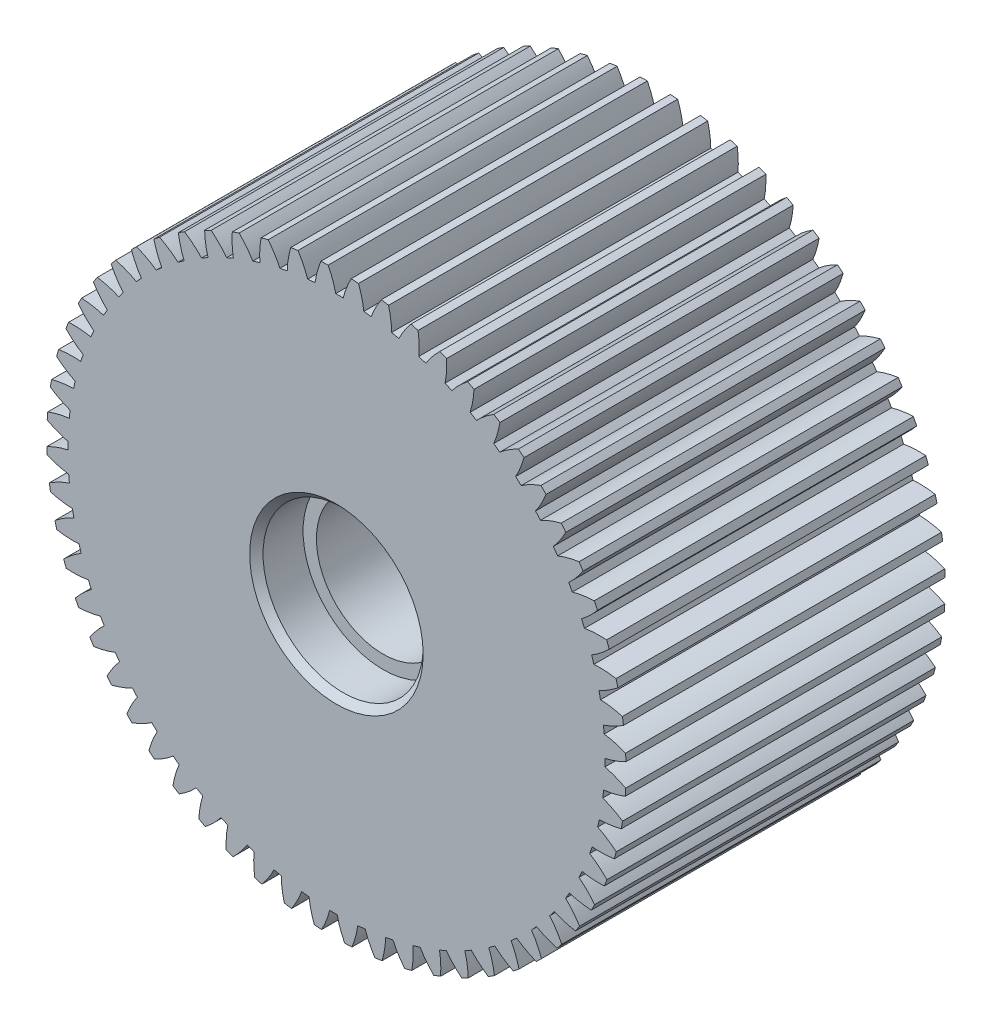
SolidWorks part; units mm, degrees
material "PLA"
ref_plane "Front Plane" through (0, 0, 0) normal (0, 0, 1) x (1, 0, 0)
ref_plane "Top Plane" through (0, 0, 0) normal (0, 1, 0) x (1, 0, 0)
ref_plane "Right Plane" through (0, 0, 0) normal (1, 0, 0) x (0, 0, -1)
sketch "Sketch1" plane through (0, 0, 0) normal (0, 0, 1) x (1, 0, 0)
  circle A0 centre (0, 0) radius 21.7
  dimension "D1" = 43.4
extrude "Boss-Extrude1" add sketch "Sketch1" along normal mid plane 23.9129
sketch "Sketch2" plane through (0, 0, 0) normal (0, 0, 1) x (1, 0, 0)
  line L0 (0, 0) -> (19.7335, 0) construction
  line L1 (0, 0) -> (20.9987, -0.2368) construction
  line L2 (0, 0) -> (19.7285, -0.445) construction
  line L3 (19.7335, 0) -> (20.125, 0)
  line L4 (19.7285, -0.445) -> (20.1199, -0.4538)
  circle A0 centre (0, 0) radius 21 construction
  circle A1 centre (0, 0) radius 19.7335 construction
  circle A2 centre (0, 0) radius 20.125
  circle A3 centre (0, 0) radius 21.7 construction
  circle A4 centre (0, 0) radius 21.7
  spline S0 degree 4 poles (19.7335, 0) (19.7403, 0.0001) (19.7592, 0.0007) (19.7949, 0.0029) (19.8532, 0.0083) (19.9272, 0.0177) (20.0227, 0.0326) (20.1349, 0.0538) (20.2577, 0.0809) (20.3908, 0.1144) (20.523, 0.1515) (20.6543, 0.1919) (20.7846, 0.2351) (20.9418, 0.291) (21.1292, 0.3629) (21.3467, 0.4541) (21.5913, 0.5659) (21.8383, 0.6888) (22.0793, 0.8169) (22.3203, 0.9546) (22.5517, 1.0937) (22.7893, 1.2466) (23.0071, 1.3919) (23.2479, 1.5639) (23.4412, 1.7054) (23.6925, 1.9016) (23.8398, 2.0204) (24.0108, 2.1626) (24.086, 2.2275) (24.1324, 2.2674) knots 0 0 0 0 0 0.005377 0.015084 0.028532 0.04661 0.064855 0.092111 0.119476 0.146842 0.174209 0.201575 0.228941 0.256307 0.307035 0.361767 0.4165 0.471232 0.525964 0.580697 0.635429 0.690161 0.744894 0.799626 0.854358 0.909091 0.954545 1 1 1 1 1 construction
  spline S1 degree 4 poles (19.7335, 0) (19.7403, 0.0001) (19.7592, 0.0007) (19.7949, 0.0029) (19.8532, 0.0083) (19.9272, 0.0177) (20.0227, 0.0326) (20.1349, 0.0538) (20.2577, 0.0809) (20.3908, 0.1144) (20.523, 0.1515) (20.6543, 0.1919) (20.7846, 0.2351) (20.9418, 0.291) (21.1292, 0.3629) (21.3467, 0.4541) (21.5913, 0.5659) (21.8383, 0.6888) (22.0793, 0.8169) (22.3203, 0.9546) (22.5517, 1.0937) (22.7893, 1.2466) (23.0071, 1.3919) (23.2479, 1.5639) (23.4412, 1.7054) (23.638, 1.8591) (23.7334, 1.935) (23.7819, 1.9742) knots 0 0 0 0 0 0.005377 0.015084 0.028532 0.04661 0.064855 0.092111 0.119476 0.146842 0.174209 0.201575 0.228941 0.256307 0.307035 0.361767 0.4165 0.471232 0.525964 0.580697 0.635429 0.690161 0.744894 0.799626 0.854358 0.909091 0.909091 0.909091 0.909091 0.909091
  spline S2 degree 4 poles (19.7285, -0.445) (19.7353, -0.4452) (19.7542, -0.4462) (19.7898, -0.4493) (19.8479, -0.456) (19.9218, -0.467) (20.0169, -0.4841) (20.1285, -0.5078) (20.2507, -0.5376) (20.383, -0.5742) (20.5143, -0.6143) (20.6447, -0.6576) (20.774, -0.7037) (20.9299, -0.7631) (21.1156, -0.8393) (21.331, -0.9354) (21.5731, -1.0527) (21.8172, -1.181) (22.0553, -1.3146) (22.2931, -1.4577) (22.5213, -1.602) (22.7554, -1.7601) (22.9699, -1.9104) (23.2067, -2.0877) (23.3968, -2.2335) (23.6436, -2.4354) (23.7882, -2.5574) (23.9559, -2.7035) (24.0297, -2.7701) (24.0751, -2.811) knots 0 0 0 0 0 0.005377 0.015084 0.028532 0.04661 0.064855 0.092111 0.119476 0.146842 0.174209 0.201575 0.228941 0.256307 0.307035 0.361767 0.4165 0.471232 0.525964 0.580697 0.635429 0.690161 0.744894 0.799626 0.854358 0.909091 0.954545 1 1 1 1 1 construction
  spline S3 degree 4 poles (19.7285, -0.445) (19.7353, -0.4452) (19.7542, -0.4462) (19.7898, -0.4493) (19.8479, -0.456) (19.9218, -0.467) (20.0169, -0.4841) (20.1285, -0.5078) (20.2507, -0.5376) (20.383, -0.5742) (20.5143, -0.6143) (20.6447, -0.6576) (20.774, -0.7037) (20.9299, -0.7631) (21.1156, -0.8393) (21.331, -0.9354) (21.5731, -1.0527) (21.8172, -1.181) (22.0553, -1.3146) (22.2931, -1.4577) (22.5213, -1.602) (22.7554, -1.7601) (22.9699, -1.9104) (23.2067, -2.0877) (23.3968, -2.2335) (23.5901, -2.3916) (23.6837, -2.4696) (23.7314, -2.51) knots 0 0 0 0 0 0.005377 0.015084 0.028532 0.04661 0.064855 0.092111 0.119476 0.146842 0.174209 0.201575 0.228941 0.256307 0.307035 0.361767 0.4165 0.471232 0.525964 0.580697 0.635429 0.690161 0.744894 0.799626 0.854358 0.909091 0.909091 0.909091 0.909091 0.909091
  dimension "D1" = 42
  dimension "D2" = 39.4671
  dimension "D3" = 40.25
  dimension "D4" = 0.646
  dimension "D5" = 0.646
extrude "Cut-Extrude1" cut sketch "Sketch2" against normal through all both and the other way through all contours A2 S3 A4 S1 region at (21.0522, -0.2374, 0)
pattern_circular "CirPattern2" count 60 over 360 about axis through (0, 0, -11.9565) along (0, 0, 1) of "Cut-Extrude1"
sketch "Sketch3" plane through (0, 0, 11.9565) normal (0, 0, 1) x (1, 0, 0)
  circle A0 centre (0, 0) radius 5
  dimension "D1" = 10
extrude "Cut-Extrude2" cut sketch "Sketch3" against normal through all both and the other way through all
sketch "Sketch4" plane through (0, 0, 11.9565) normal (0, 0, 1) x (1, 0, 0)
  circle A0 centre (0, 0) radius 6
  dimension "D1" = 12
extrude "Cut-Extrude3" cut sketch "Sketch4" against normal blind 3.5 contours A0
mirror "Mirror2" about plane through (0, 0, 0) normal (0, 0, 1) of "Cut-Extrude3"
chamfer "Chamfer1" distance 0.5 angle 45 2 edges at (6, 0, 11.9565) (6, 0, -11.9565)
equation "\"Ns\" = 48"
equation "\"module\" = 0.7"
equation "\"pressure angle\" = 20.0"
equation "\"h_a\" = 0.7"
equation "\"h_b\" = 0.875"
equation "\"clr_tip_root\" = 0.17500000000000004"
equation "\"dp_s\" = 33.599999999999994"
equation "\"db_s\" = 31.57367205840652"
equation "\"D1@Sketch1\"=\"dp_fs\" + 2*\"h_a\""
equation "\"fw_s_calc\" = 5.685933367726717"
equation "\"D1@Boss-Extrude1\"=\"fw_fs\"-2mm"
equation "\"D1@Sketch2\"=\"dp_fs\""
equation "\"D2@Sketch2\"=\"db_fs\""
equation "\"D3@Sketch2\"=\"dp_fs\"- 2*\"h_b\""
equation "\"alpha_s\" = 0.8539582918412343"
equation "\"D4@Sketch2\"=\"beta_fs\"/2"
equation "\"beta_s\" = 2.0420834163175314"
equation "\"D5@Sketch2\"=\"beta_fs\"/2"
equation "\"D1@CirPattern2\"=\"Ns_fs\""
equation "\"pressure_angle\" = 20.0"
equation "\"h_f\" = 0.875"
equation "\"bearing_ID\" = 70"
equation "\"bearing_OD\" = 90"
equation "\"bearing_height\" = 10"
equation "\"clearance_planet\" = 1.5"
equation "\"case_dist\" = 6.5"
equation "\"Motor_case_OD_max\" = 131.3"
equation "\"case_mounting_PCD\" = 123.8"
equation "\"bearing mount thickness\" = 8"
equation "\"case_mounting_hole_dia\" = 3"
equation "\"output_mounting_PCD\" = 98"
equation "\"output_mounting_hole_dia\" = 4"
equation "\"clearance_case_mount_holes_shell_thickness\" = 1"
equation "\"motor_case_OD_base\" = 121.8"
equation "\"sec_carrier_thickness\" = 5"
equation "\"sun_coupler_hub_thickness\" = 4"
equation "\"clearance_sun_coupler_sec_carrier\" = 1.5"
equation "\"clearance_motor_and_case\" = 5"
equation "\"motor_OD\" = 106.8"
equation "\"Motor_case_thickness\" = 2.5"
equation "\"Motor_case_ID\" = 116.8"
equation "\"case_mounting_hole_shift\" = 1.0"
equation "\"output_mounting_nut_wrench_size\" = 7"
equation "\"output_mounting_nut_thickness\" = 3.2"
equation "\"case_mounting_hole_allen_socket_dia\" = 5.5"
equation "\"output_mounting_nut_depth\" = 3"
equation "\"case_mounting_bolt_depth\" = 4.5"
equation "\"ring_radial_thickness\" = 5"
equation "\"ring_to_chamfer_clearance\" = 1.5"
equation "\"Motor_case_OD_base_to_chamfer\" = 5"
equation "\"pattern_offset_from_motor_case_OD_base\" = 3"
equation "\"pattern_bulge_dia\" = 3"
equation "\"pattern_num_bulge\" = 18"
equation "\"pattern_depth\" = 2"
equation "\"motor_height\" = 47.6"
equation "\"case_mounting_wrench_size\" = 5.5"
equation "\"case_mounting_nut_clearance\" = 2"
equation "\"base_plate_thickness\" = 4"
equation "\"case_mounting_nut_thickness\" = 2.4"
equation "\"case_mounting_surface_height\" = 4"
equation "\"motor_mount_hole_PCD\" = 40"
equation "\"motor_mount_hole_dia\" = 5"
equation "\"motor_mount_hole_num\" = 4"
equation "\"central_hole_offset_from_motor_mount_PCD\" = 5"
equation "\"wire_slot_dist_from_center\" = 45.5"
equation "\"wire_slot_length\" = 10"
equation "\"wire_slot_radius\" = 3"
equation "\"driver_upper_holes_dist_from_center\" = 29"
equation "\"driver_lower_holes_dist_from_center\" = 13"
equation "\"driver_side_holes_dist_from_center\" = 22.5"
equation "\"driver_mount_holes_dia\" = 3"
equation "\"driver_mount_inserts_OD\" = 4.8"
equation "\"driver_mount_thickness\" = 1.5"
equation "\"driver_mount_height\" = 6"
equation "\"air_flow_hole_offset\" = 3"
equation "\"num_planet\" = 4"
equation "\"planet_pin_bolt_dia\" = 5"
equation "\"planet_pin_socket_head_dia\" = 8.5"
equation "\"carrier_PCD\" = 61.599999999999994"
equation "\"planet_shaft_dia\" = 8"
equation "\"planet_shaft_step_offset\" = 1"
equation "\"carrier_trapezoidal_support_sun_offset\" = 5"
equation "\"carrier_trapezoidal_support_hole_PCD_offset_bearing_ID\" = 4"
equation "\"carrier_trapezoidal_support_hole_dia\" = 3"
equation "\"carrier_trapezoidal_support_hole_socket_head_dia\" = 5.5"
equation "\"carrier_bearing_step_width\" = 1.5"
equation "\"standard_clearance_1_5mm\" = 1.5"
equation "\"standard_fillet_1_5mm\" = 1.5"
equation "\"sun_shaft_bearing_OD\" = 16"
equation "\"sun_shaft_bearing_width\" = 5"
equation "\"standard_bearing_insertion_chamfer\" = 0.5"
equation "\"carrier_trapezoidal_support_hole_wrench_size\" = 5.5"
equation "\"planet_pin_bolt_wrench_size\" = 8"
equation "\"planet_bearing_OD\" = 12"
equation "\"planet_bearing_width\" = 3.5"
equation "\"planet_bore\" = 10"
equation "\"motor_output_hole_PCD\" = 23"
equation "\"motor_output_hole_dia\" = 4"
equation "\"motor_output_hole_num\" = 4"
equation "\"sun_shaft_bearing_ID\" = 8"
equation "\"sun_hub_dia\" = 30.0"
equation "\"sun_central_bolt_dia\" = 5"
equation "\"sun_central_bolt_socket_head_dia\" = 8.5"
equation "\"fw_s_used\" = 63.40868620995457"
equation "\"motor_output_hole_CSK_OD\" = 8"
equation "\"motor_output_hole_CSK_head_height\" = 2.0"
equation "\"Np_b\" = 40"
equation "\"dp_p_b\" = 28.0"
equation "\"db_p_b\" = 26.311393382005434"
equation "\"fw_p_s\" = 25.912913082891553"
equation "\"alpha_p_b\" = 0.8539582918412485"
equation "\"beta_p_b\" = 2.792083416317503"
equation "\"bearing_retainer_thickness\" = 2"
equation "\"Np_s\" = 28"
equation "\"fw_p_b\" = 29.99577312706301"
equation "\"dp_p_s\" = 19.599999999999998"
equation "\"db_p_s\" = 18.417975367403802"
equation "\"alpha_p_s\" = 0.8539582918412592"
equation "\"beta_p_s\" = 4.7206548448889105"
equation "\"Cut-Extrude9\"= IIF ( ( \"Ns\" * \"module\" + 2 * \"h_a\" ) < ( \"motor_output_hole_PCD\" - \"motor_output_hole_CSK_OD\" ) , \"suppressed\" , \"unsuppressed\" )"
equation "\"Nr_b\" = 128"
equation "\"dp_r_b\" = 89.6"
equation "\"db_r_b\" = 84.19645882241738"
equation "\"fw_r_b\" = 29.99577312706301"
equation "\"alpha_r_b\" = 0.8539582918412556"
equation "\"beta_r_b\" = 3.114166583682511"
equation "\"ring_OD_b\" = 99.6"
equation "\"Fillet10\"= IIF ( \"ring_OD_b\" > ( \"bearing_OD\" + 2 * \"bearing mount thickness\" ) , \"suppressed\" , \"unsuppressed\" )"
equation "\"Fillet11\"= IIF ( \"ring_OD_b\" < ( \"bearing_OD\" + 2 * \"bearing mount thickness\" ) , \"suppressed\" , \"unsuppressed\" )"
equation "\"Nr_s\" = 116"
equation "\"clr_tip_root_s\" = 0.17500000000000004"
equation "\"dp_r_s\" = 81.19999999999999"
equation "\"db_r_s\" = 76.30304080781575"
equation "\"fw_r_s\" = 24.412913082891553"
equation "\"alpha_r_s\" = 0.8539582918412556"
equation "\"beta_r_s\" = 3.259640721613546"
equation "\"small_ring_case_thickness\" = 4"
equation "\"carrier_thickness\" = 4"
equation "\"small_ring_output_wall_thickness\" = 5"
equation "\"small_ring_output_wall_to_bearing_shaft_attachement_hole_dia\" = 4"
equation "\"small_ring_output_wall_to_bearing_shaft_attachement_hole_depth\" = 6.5"
equation "\"small_ring_output_wall_to_bearing_shaft_attachement_nut_wrench\" = 7"
equation "\"small_ring_output_wall_to_bearing_shaft_attachement_nut_thickness\" = 3.2"
equation "\"small_ring_output_wall_to_bearing_shaft_attachement_hole_pcd\" = 12"
equation "\"small_ring_output_wall_to_bearing_shaft_attachement_hole_num\" = 3"
equation "\"small_ring_output_wall_to_bearing_shaft_attachement_hole_CSK_OD\" = 8"
equation "\"small_ring_output_wall_to_bearing_shaft_attachement_hole_CSK_head_height\" = 2.0"
equation "\"carrier_small_ring_inner_bearing_ID\" = 20"
equation "\"carrier_small_ring_inner_bearing_OD\" = 32"
equation "\"carrier_small_ring_inner_bearing_height\" = 7"
equation "\"carrier_small_ring_inner_bearing_flap\" = 2"
equation "\"gear_casing_big_ring_to_bearing_dist\" = 34.91291308289155"
equation "\"gear_casing_thickness\" = 4"
equation "\"tight_clearance_3DP\" = 0.4"
equation "\"loose_clearance_3DP\" = 0.8"
equation "\"Cut-Extrude10\"= IIF ( ( \"Ns\" * \"module\" - 2 * \"h_a\" ) < ( \"motor_output_hole_PCD\" + \"motor_output_hole_dia\" + \"standard_clearance_1_5mm\" * 4 / 3 ) , \"suppressed\" , \"unsuppressed\" )"
equation "\"Ns_fs\" = 60"
equation "\"dp_fs\" = 42.0"
equation "\"db_fs\" = 39.46709007300815"
equation "\"alpha_fs\" = 0.8539582918412592"
equation "\"beta_fs\" = 1.2920834163174817"
equation "\"fw_fs\" = 25.912913082891553"
equation "\"num_idler\" = 4"
equation "\"idler_angle_offset\" = 45.0"
equation "\"fs_bore_dia\" = 31.599999999999998"
equation "\"fs_bore_wall\" = 2.6500000000000004"
equation "\"fs_axial_clearance\" = 0.8"
equation "\"D1@Sketch3\"=\"planet_bore\""
equation "\"D1@Sketch4\"=\"planet_bearing_OD\""
equation "\"D1@Cut-Extrude3\"=\"planet_bearing_width\""
equation "\"D1@Chamfer1\"=\"standard_bearing_insertion_chamfer\""
